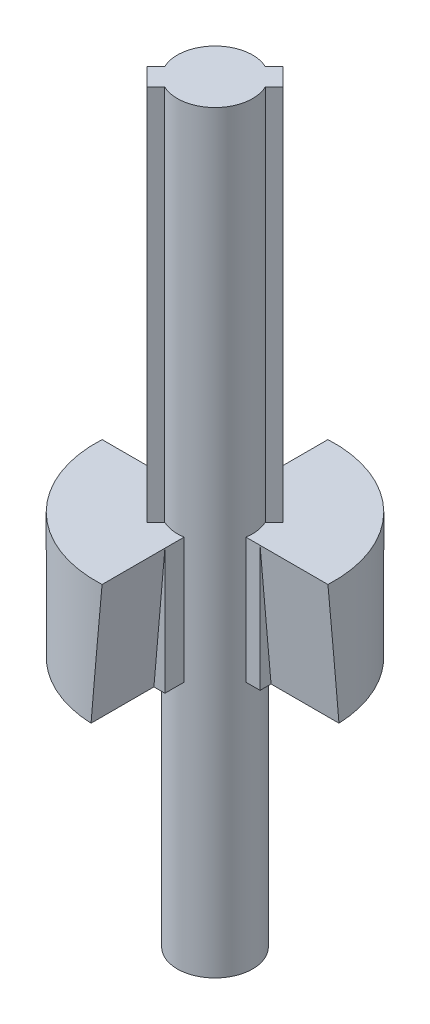
SolidWorks part; units mm, degrees
ref_plane "Front Plane" through (0, 0, 0) normal (0, 0, 1) x (1, 0, 0)
ref_plane "Top Plane" through (0, 0, 0) normal (0, 1, 0) x (1, 0, 0)
ref_plane "Right Plane" through (0, 0, 0) normal (1, 0, 0) x (0, 0, -1)
sketch "Sketch1" plane through (0, 0, 0) normal (0, 1, 0) x (1, 0, 0)
  line L0 (0, 12.1683) -> (0, -14.062) construction
  line L1 (-13.6994, 0) -> (17.366, 0) construction
  line L2 (0.0066, 5) -> (3.271, 5)
  line L3 (5, 3.271) -> (5, 0.0066)
  line L5 (4.5, 6.229) -> (4.5, 9.4934)
  line L6 (6.229, 4.5) -> (9.4934, 4.5)
  arc A0 (5, 0.0066) -> (0.0066, 5) centre (4.75, 4.75) cw
  arc A1 (5, 3.271) -> (6.229, 4.5) centre (4.75, 4.75) ccw
  arc A2 (4.5, 9.4934) -> (9.4934, 4.5) centre (4.75, 4.75) cw
  arc A3 (4.5, 6.229) -> (3.271, 5) centre (4.75, 4.75) ccw
  dimension "D2" = 1.5
  dimension "D3" = 4.75
  dimension "D1" = 4.75
  dimension "D4" = 0.25
  dimension "D5" = 0.25
  dimension "D6" = 0.25
  dimension "D7" = 0.25
extrude "Boss-Extrude1" add sketch "Sketch1" along normal mid plane 30 contours A0 L2 A3 L5 A2 L6 A1 L3
sketch "Sketch2" plane through (0, 15, 0) normal (0, 1, 0) x (1, 0, 0)
  circle A0 centre (4.75, 4.75) radius 1.5
  circle A1 centre (4.75, 4.75) radius 4.75
extrude "Cut-Extrude1" cut sketch "Sketch2" against normal blind 15
sketch "Sketch3" plane through (0, -15, -15) normal (0, 1, 0) x (1, 0, 0)
  circle A0 centre (4.75, -10.25) radius 1.5
  circle A1 centre (4.75, -10.25) radius 4.75
  circle A3 centre (4.75, -10.25) radius 1.5 construction
extrude "Cut-Extrude2" cut sketch "Sketch3" along normal blind 10
ref_axis "Axis1" through (4.75, 15, -4.75) along (0, -1, 0)
sketch "Sketch4" plane through (0, 15, 0) normal (0, 1, 0) x (1, 0, 0)
  line L0 (8.743, 8.743) -> (1.3187, 1.3187) construction
  line L1 (-5.225, 0) -> (5.225, 0) construction
  line L2 (4.1036, 3.3964) -> (3.75, 3.0429)
  line L3 (3.75, 3.0429) -> (3.0429, 3.75)
  line L4 (3.0429, 3.75) -> (3.3964, 4.1036)
  line L5 (2.7846, 6.7154) -> (6.7863, 2.7137) construction
  line L6 (5.75, 6.4571) -> (5.3964, 6.1036)
  line L7 (6.4571, 5.75) -> (5.75, 6.4571)
  line L8 (6.1036, 5.3964) -> (6.4571, 5.75)
  circle A0 centre (4.75, 4.75) radius 1.5 construction
  arc A1 (3.3964, 4.1036) -> (4.1036, 3.3964) centre (4.75, 4.75) ccw
  arc A2 (5.3964, 6.1036) -> (6.1036, 5.3964) centre (4.75, 4.75) cw
  point P13 (3.9268, 3.2197)
  dimension "D3" = 0.5
  dimension "D1" = 45
  dimension "D2" = 1
extrude "Boss-Extrude2" add sketch "Sketch4" against normal up to next
ref_plane "Plane1" through (0, 0, -0.0066) normal (0, 0, 1) x (1, 0, 0)
ref_plane "Plane2" through (0, 0, -9.4934) normal (0, 0, 1) x (1, 0, 0)
ref_plane "Plane3" through (0.0066, 0, 0) normal (1, 0, 0) x (0, 0, -1)
ref_plane "Plane4" through (9.4934, 0, 0) normal (1, 0, 0) x (0, 0, -1)
sketch "Sketch5" plane through (0, 0, -0.0066) normal (0, 0, 1) x (1, 0, 0)
  line L0 (5, 0) -> (4.5626, -5)
  line L1 (4.5626, -5) -> (5, -5)
  line L2 (5, -5) -> (5, 0)
  dimension "D1" = 5
extrude "Cut-Extrude4" cut sketch "Sketch5" against normal blind 2.5 and the other way blind 0.25
pattern_circular "CirPattern1" count 2 over 360 about axis through (4.75, 15, -4.75) along (0, -1, 0) of "Cut-Extrude4"
sketch "Sketch10" plane through (0.0066, 0, 0) normal (1, 0, 0) x (0, 0, -1)
  line L0 (5, -5) -> (5, 0)
  line L1 (5, 0) -> (4.5626, -5)
  line L2 (4.5626, -5) -> (5, -5)
  dimension "D1" = 5
extrude "Cut-Extrude5" cut sketch "Sketch10" along normal blind 2.7 and the other way blind 2.5
pattern_circular "CirPattern2" count 2 over 360 about axis through (4.75, 15, -4.75) along (0, -1, 0) of "Cut-Extrude5"
